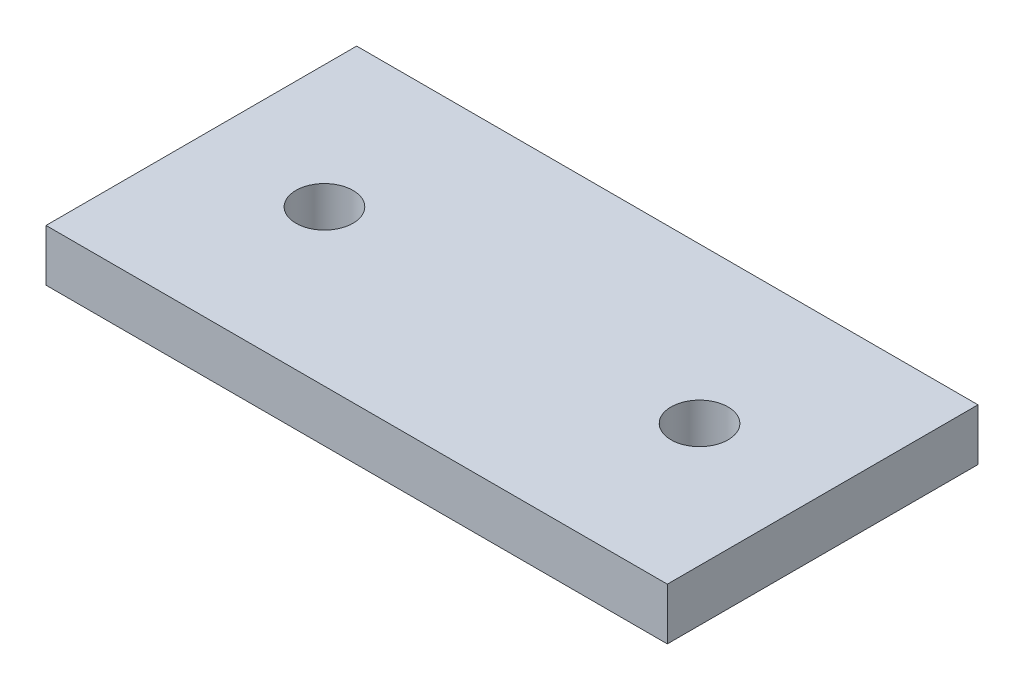
SolidWorks part; units mm, degrees
ref_plane "Front Plane" through (0, 0, 0) normal (0, 0, 1) x (1, 0, 0)
ref_plane "Top Plane" through (0, 0, 0) normal (0, 1, 0) x (1, 0, 0)
ref_plane "Right Plane" through (0, 0, 0) normal (1, 0, 0) x (0, 0, -1)
sketch "Sketch1" plane through (0, 0, 0) normal (0, 1, 0) x (1, 0, 0)
  line L1 (-38.1, 19.05) -> (38.1, 19.05)
  line L2 (-38.1, 19.05) -> (-38.1, -19.05)
  line L3 (-38.1, -19.05) -> (38.1, -19.05)
  line L4 (38.1, 19.05) -> (38.1, -19.05)
  line L5 (-38.1, 19.05) -> (38.1, -19.05) construction
  line L6 (-38.1, -19.05) -> (38.1, 19.05) construction
  point P0 (0, 0)
  dimension "D1" = 76.2
  dimension "D2" = 38.1
extrude "Boss-Extrude1" add sketch "Sketch1" along normal blind 6.35
hole_wizard "M6 Clearance Hole1" positions "Sketch2" profile "Sketch3" hole size "M6" standard "ANSI Metric" end condition through all
sketch "Sketch2" plane through (0, 6.35, 0) normal (0, 1, 0) x (1, 0, 0)
  line L0 (-23, 0) -> (0, 0) construction
  line L1 (0, 0) -> (23, 0) construction
  point P0 (-23, 0)
  point P2 (23, 0)
  dimension "D1" = 46
sketch "Sketch3" plane through (-23, 6.35, 0) normal (1, 0, 0) x (0, 0, 1)
  line L0 (0, 0) -> (0, 6.35)
  line L1 (0, 6.35) -> (3.5, 6.35)
  line L2 (3.5, 6.35) -> (3.5, 0)
  line L5 (3.5, 0) -> (0, 0)
  line L11 (0, -6.35) -> (0, 107.95) construction
  dimension "Thru Hole Dia." = 7
  dimension "Thru Hole Depth" = 6.35
equation "\"width\" = 3in"
equation "\"D1@Sketch1\"=\"width\""
equation "\"depth\" = 1.5in"
equation "\"height\"= .25in"
equation "\"D1@Boss-Extrude1\"= \"height\""
equation "\"D2@Sketch1\"= \"depth\""
equation "\"hole_dist\"= 46mm"
equation "\"D1@Sketch2\"=\"hole_dist\""
